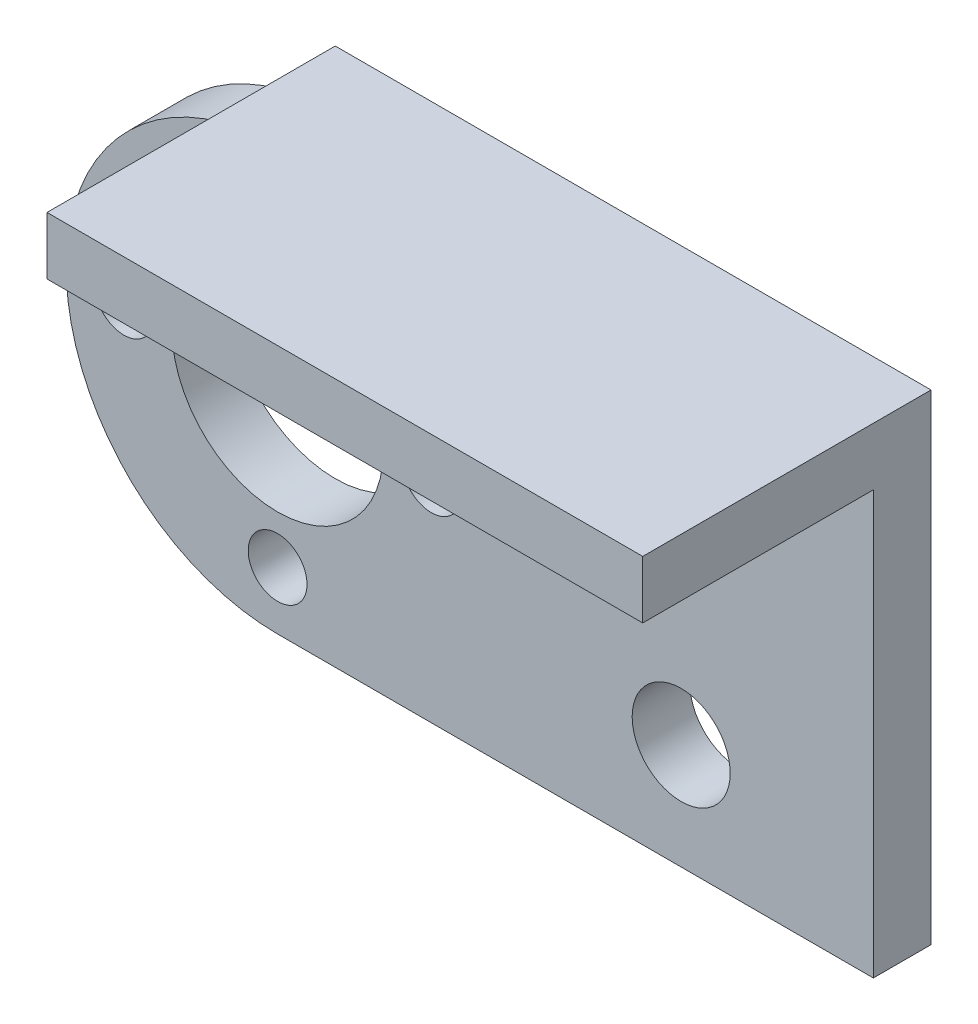
SolidWorks part; units mm, degrees
ref_plane "Front Plane" through (0, 0, 0) normal (0, 0, 1) x (1, 0, 0)
ref_plane "Top Plane" through (0, 0, 0) normal (0, 1, 0) x (1, 0, 0)
ref_plane "Right Plane" through (0, 0, 0) normal (1, 0, 0) x (0, 0, -1)
sketch "Sketch1" plane through (0, 0, 0) normal (0, 0, 1) x (1, 0, 0)
  line L0 (0, 0) -> (0, 8) construction
  line L2 (0, -11) -> (11, -11)
  line L3 (0, 11) -> (11, 11)
  line L4 (11, 11) -> (31, 11)
  line L5 (11, -11) -> (31, -11)
  line L7 (31, -11) -> (31, 11)
  arc A3 (0, 11) -> (0, -11) centre (0, 0) ccw
  circle A4 centre (0, 8) radius 1.53
  circle A5 centre (8, 0) radius 1.53
  circle A6 centre (0, -8) radius 1.53
  circle A7 centre (-8, 0) radius 1.53
  circle A8 centre (0, 0) radius 5.5
  point P19 (0, 0)
  dimension "D1" = 4
extrude "Boss-Extrude1" add sketch "Sketch1" along normal blind 3
sketch "Sketch2" plane through (0, 0, 0) normal (0, 0, 1) x (1, 0, 0)
  line L0 (31, 0) -> (11, 0) construction
  line L1 (31, -11) -> (31, 11) construction
  line L2 (21, 0) -> (21, 11) construction
  line L3 (31, 11) -> (0, 11) construction
  circle A0 centre (21, 5.5) radius 2.55
  circle A1 centre (21, -5.5) radius 2.55
extrude "Cut-Extrude1" cut sketch "Sketch2" along normal blind 10
sketch "Sketch4" plane through (0, 0, 0) normal (0, 0, 1) x (1, 0, 0)
  line L1 (31, 11) -> (0, 11)
  line L2 (31, 11) -> (31, 14)
  line L3 (31, 14) -> (0, 14)
  line L4 (0, 11) -> (0, 14)
extrude "Boss-Extrude2" add sketch "Sketch4" along normal blind 15
fillet "Fillet1" radius 4 1 edges at (0, 11, 1.5)
fillet "Fillet4" radius 1 1 edges at (0, 12.5, 3)
